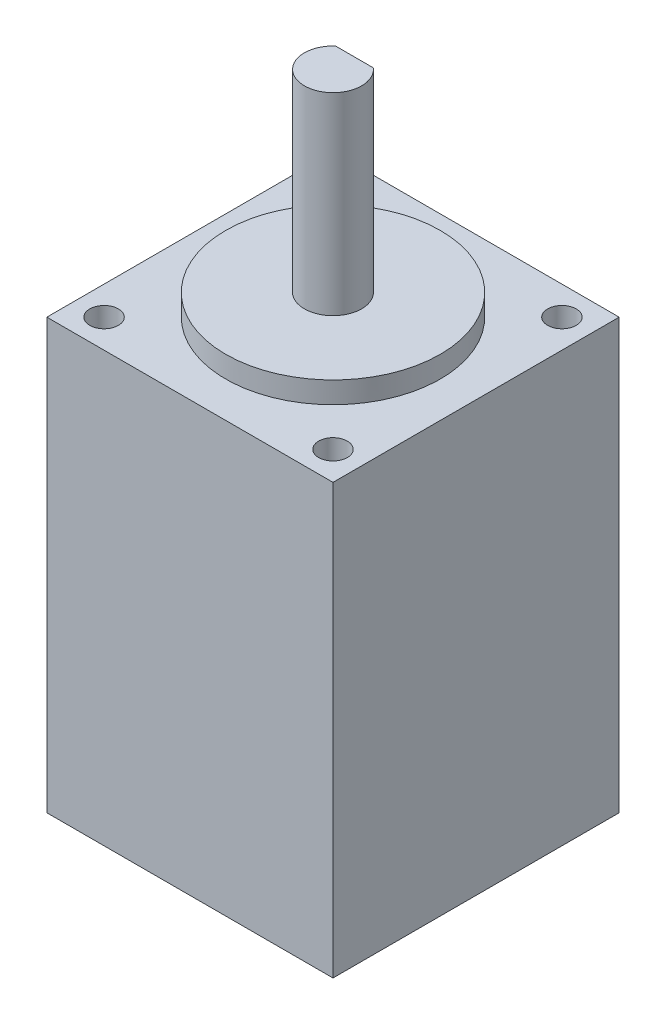
SolidWorks part; units mm, degrees
ref_plane "Front Plane" through (0, 0, 0) normal (0, 0, 1) x (1, 0, 0)
ref_plane "Top Plane" through (0, 0, 0) normal (0, 1, 0) x (1, 0, 0)
ref_plane "Right Plane" through (0, 0, 0) normal (1, 0, 0) x (0, 0, -1)
sketch "Sketch1" plane through (0, 0, 0) normal (0, 1, 0) x (1, 0, 0)
  line L1 (0, 0) -> (20, 0)
  line L2 (0, 0) -> (0, 20)
  line L3 (0, 20) -> (20, 20)
  line L4 (20, 0) -> (20, 20)
  dimension "D1" = 20
extrude "Boss-Extrude1" add sketch "Sketch1" along normal blind 30
sketch "Sketch2" plane through (0, 30, 0) normal (0, 1, 0) x (1, 0, 0)
  line L0 (10, 20) -> (10, 0) construction
  line L1 (20, 20) -> (0, 20) construction
  line L2 (0, 0) -> (20, 0) construction
  line L3 (0, 10) -> (20, 10) construction
  line L4 (0, 20) -> (0, 0) construction
  line L5 (20, 0) -> (20, 20) construction
  line L6 (2, 2) -> (10, 2) construction
  line L7 (2, 18) -> (10, 18) construction
  line L8 (18, 2) -> (18, 10) construction
  line L9 (18, 18) -> (18, 10) construction
  line L10 (18, 18) -> (10, 18) construction
  line L11 (2, 2) -> (2, 10) construction
  line L12 (2, 18) -> (2, 10) construction
  line L13 (18, 2) -> (10, 2) construction
  circle A0 centre (2, 18) radius 1
  circle A1 centre (18, 18) radius 1
  circle A2 centre (18, 2) radius 1
  circle A3 centre (2, 2) radius 1
  dimension "D2" = 2
  dimension "D1" = 16
extrude "Cut-Extrude1" cut sketch "Sketch2" against normal blind 3.5
sketch "Sketch3" plane through (0, 30, 0) normal (0, 1, 0) x (1, 0, 0)
  line L0 (0, 10) -> (20, 10) construction
  line L1 (0, 20) -> (0, 0) construction
  line L2 (20, 0) -> (20, 20) construction
  circle A0 centre (10, 10) radius 7.5
  dimension "D1" = 15
extrude "Boss-Extrude2" add sketch "Sketch3" along normal blind 1.5
sketch "Sketch4" plane through (0, 31.5, 0) normal (0, 1, 0) x (1, 0, 0)
  line L0 (2.5, 10) -> (17.5, 10) construction
  circle A0 centre (10, 10) radius 7.5 construction
  circle A1 centre (10, 10) radius 2
  dimension "D1" = 4
extrude "Boss-Extrude3" add sketch "Sketch4" along normal blind 13.5
sketch "Sketch5" plane through (0, 45, 0) normal (0, 1, 0) x (1, 0, 0)
  line L0 (8.6771, 11.5) -> (11.3229, 11.5)
  line L1 (10, 8) -> (12.7751, 8) construction
  circle A0 centre (10, 10) radius 2 construction
  arc A1 (8.6771, 11.5) -> (11.3229, 11.5) centre (10, 10) cw
  circle M3 centre (10, 10) radius 2
  dimension "D1" = 3.5
extrude "Cut-Extrude2" cut sketch "Sketch5" against normal up to surface (13.5 mm away) contours L0 M3 region at (10, 45, -11.7023) up to face at (10, 31.5, -8)
